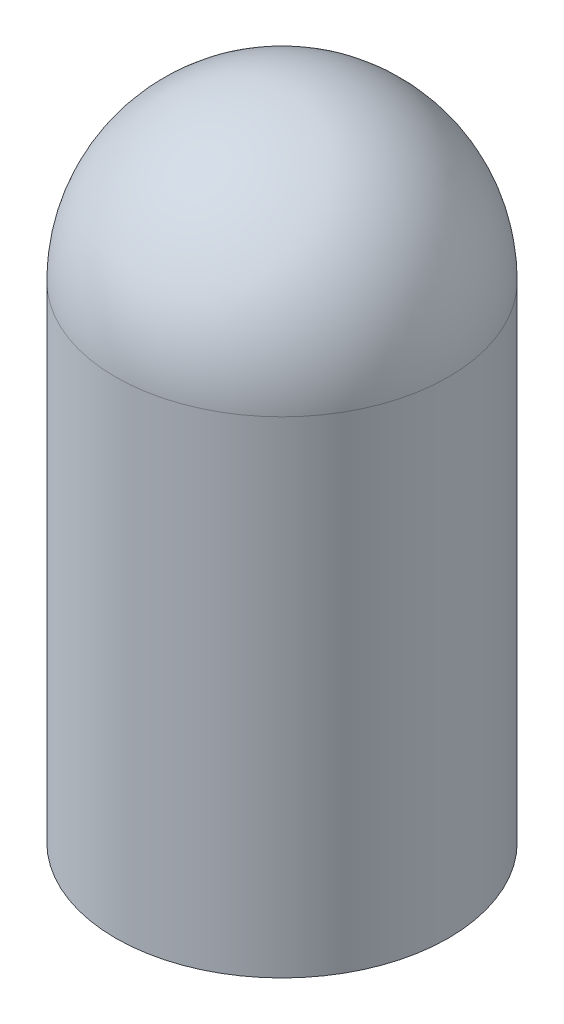
SolidWorks part; units mm, degrees
ref_plane "Front Plane" through (0, 0, 0) normal (0, 0, 1) x (1, 0, 0)
ref_plane "Top Plane" through (0, 0, 0) normal (0, 1, 0) x (1, 0, 0)
ref_plane "Right Plane" through (0, 0, 0) normal (1, 0, 0) x (0, 0, -1)
sketch "Sketch1" plane through (0, 0, 0) normal (0, 0, 1) x (1, 0, 0)
  line L0 (25.5, 74.5) -> (25.5, 0)
  line L1 (0, 130.9364) -> (0, -70.7976) construction
  line L2 (0, 0) -> (25.5, 0)
  line L3 (0, 0) -> (0, 100)
  arc A0 (25.5, 74.5) -> (0, 100) centre (0, 74.5) ccw
  dimension "D1" = 100
  dimension "D2" = 25.5
revolve "Revolve1" add sketch "Sketch1" angle 360 about L1
